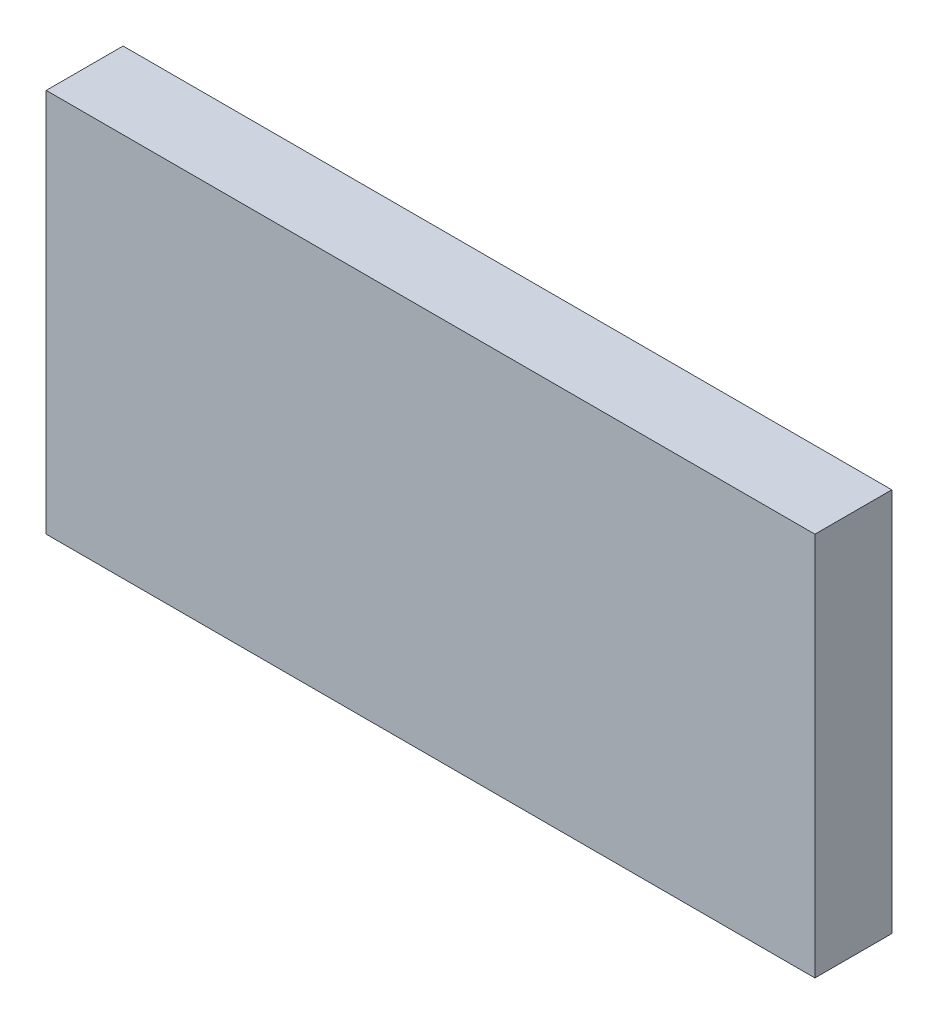
SolidWorks part; units mm, degrees
ref_plane "前视基准面" through (0, 0, 0) normal (0, 0, 1) x (1, 0, 0)
ref_plane "上视基准面" through (0, 0, 0) normal (0, 1, 0) x (1, 0, 0)
ref_plane "右视基准面" through (0, 0, 0) normal (1, 0, 0) x (0, 0, -1)
other "Configuration Table"
sketch "草图1" plane through (0, 0, 0) normal (0, 0, 1) x (1, 0, 0)
  line L1 (0, 0) -> (20, 0)
  line L2 (0, 0) -> (0, 10)
  line L3 (0, 10) -> (20, 10)
  line L4 (20, 0) -> (20, 10)
base flange "基体-法兰1" sketch "草图1" thickness 2 reverse thickness direction no parameters "D1"=2
sketch "折弯-线1" plane through (0, 0, 0) normal (0, 1, 0) x (1, 0, 0)
sketch "边界框1" plane through (0, 0, 0) normal (0, 1, 0) x (1, 0, 0)
sheet metal parameters "钣金6" thickness 2 parameters "D1"=2
flat pattern "平板型式6" [suppressed]
sketch "折弯-线2" plane through (0, 0, 0) normal (0, 1, 0) x (1, 0, 0)
sketch "边界框2" [suppressed] plane through (0, 0, 0) normal (0, 1, 0) x (1, 0, 0)
